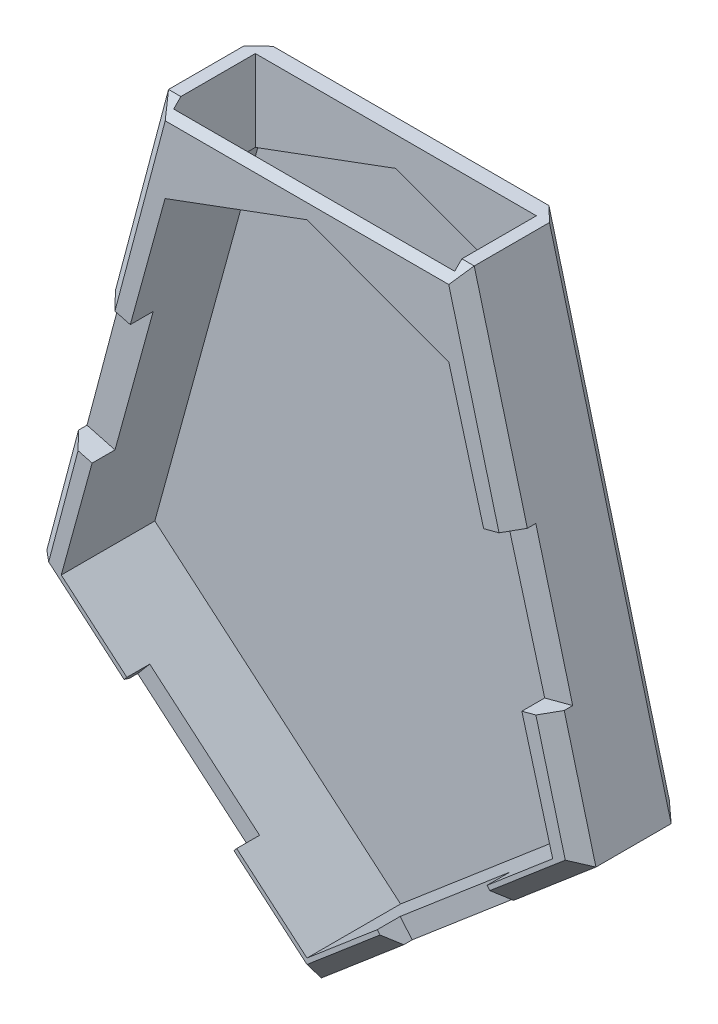
SolidWorks part; units mm, degrees
ref_plane "Front Plane" through (0, 0, 0) normal (0, 0, 1) x (1, 0, 0)
ref_plane "Top Plane" through (0, 0, 0) normal (0, 1, 0) x (1, 0, 0)
ref_plane "Right Plane" through (0, 0, 0) normal (1, 0, 0) x (0, 0, -1)
sketch "Sketch1" plane through (0, 0, 0) normal (0, 0, 1) x (1, 0, 0)
  line L0 (0.1743, 63.7646) -> (-42.2493, 63.7646)
  line L1 (-42.2493, 63.7646) -> (-59.1375, -0.0381)
  line L2 (0.1743, 63.7646) -> (17.0625, -0.0381)
  line L3 (-21.0375, 63.7646) -> (-21.0375, -70.4526) construction
  line L4 (-59.1375, -0.0381) -> (-21.0375, -32.417)
  line L5 (-21.0375, -32.417) -> (17.0625, -0.0381)
  line L6 (-42.2493, 63.7646) -> (17.0625, -0.0381) construction
  line L7 (-59.1375, -0.0381) -> (0.1743, 63.7646) construction
  line L8 (-59.1375, -0.0381) -> (17.0625, -0.0381) construction
  line L9 (-40.73, 52.4141) -> (-21.0375, 59.7084)
  line L10 (-21.0375, 59.7084) -> (-1.3451, 52.4141)
  line L11 (-1.3451, 52.4141) -> (13.0625, -0.0381)
  line L12 (13.0625, -0.0381) -> (-21.0375, -29.0176)
  line L13 (-21.0375, -29.0176) -> (-55.1375, -0.0381)
  line L14 (-55.1375, -0.0381) -> (-40.73, 52.4141)
  dimension "D1" = 76.2
  dimension "D2" = 42.4236
  dimension "D3" = 66
  dimension "D4" = 66
  dimension "D5" = 50
  dimension "D6" = 50
  dimension "D7" = 21
  dimension "D8" = 21
  dimension "D9" = 115
  dimension "D10" = 115
  dimension "D11" = 4
  dimension "D12" = 4
  dimension "D13" = 360
  dimension "D14" = 139.35
  dimension "D15" = 88.726
  dimension "D16" = 125.684
  dimension "D17" = 125.684
  dimension "D18" = 54.395
  dimension "D19" = 44.7507
  dimension "D20" = 99.282
extrude "Boss-Extrude3" add sketch "Sketch1" along normal blind 14.4395 contours L4 L5 L2 L0 L1 L13 L14 L9 L10 L11 L12 region at (7.4322, 31.5493, 0)
extrude "Boss-Extrude4" add sketch "Sketch1<5>" along normal blind 1.4532 contours L14 L13 L12 L11 L10 L9 region at (-21.0375, 16.588, 0)
sketch "Sketch1<5>" plane through (0, 0, 0) normal (0, 0, 1) x (1, 0, 0) same geometry as "Sketch1"
sketch "Sketch3" plane through (0, 63.7646, 0) normal (0, 1, 0) x (1, 0, 0)
  line L1 (-40.5393, -2.1) -> (-1.5393, -2.1)
  line L2 (-40.5393, -2.1) -> (-40.5393, -13.4395)
  line L3 (-40.5393, -13.4395) -> (-1.5393, -13.4395)
  line L4 (-1.5393, -2.1) -> (-1.5393, -13.4395)
  line L5 (-42.2493, -14.4395) -> (-42.2493, 0) construction
  line L7 (0.1743, 0) -> (-42.2493, 0) construction
  line L8 (0.1743, -14.4395) -> (-42.2493, -14.4395) construction
  dimension "D1" = 39
  dimension "D2" = 1.71
  dimension "D3" = 2.1
  dimension "D4" = 1
extrude "Cut-Extrude2" cut sketch "Sketch3" against normal blind 20 contours L2 L1 L4 L3
sketch "Sketch5" plane through (-24.8185, -29.2037, 0) normal (-0.6476, -0.762, 0) x (0.762, -0.6476, 0)
  line L0 (-45.0381, 14.4395) -> (4.9619, 14.4395) construction
  line L1 (-30.0381, 14.4395) -> (-10.0381, 14.4395)
  line L2 (-30.0381, 14.4395) -> (-30.0381, 11.2645)
  line L3 (-30.0381, 11.2645) -> (-10.0381, 11.2645)
  line L4 (-10.0381, 14.4395) -> (-10.0381, 11.2645)
  line L5 (-45.0381, 14.4395) -> (-45.0381, 0) construction
  dimension "D1" = 20
  dimension "D2" = 15
  dimension "D3" = 3.175
sketch "Sketch6" plane through (7.1741, -8.4417, 0) normal (0.6476, -0.762, 0) x (0.762, 0.6476, 0)
  line L0 (-37.0231, 14.4395) -> (12.9769, 14.4395) construction
  line L1 (-22.0231, 14.4395) -> (-2.0231, 14.4395)
  line L2 (-22.0231, 14.4395) -> (-22.0231, 11.2645)
  line L3 (-22.0231, 11.2645) -> (-2.0231, 11.2645)
  line L4 (-2.0231, 14.4395) -> (-2.0231, 11.2645)
  line L5 (12.9769, 14.4395) -> (12.9769, 0) construction
  dimension "D1" = 3.175
  dimension "D2" = 20
  dimension "D3" = 15
extrude "Cut-Extrude3" cut sketch "Sketch6" against normal blind 20
extrude "Cut-Extrude4" cut sketch "Sketch5" against normal blind 20
sketch "Sketch7" plane through (-55.256, 14.6259, 0) normal (-0.9667, 0.2559, 0) x (0, 0, 1)
  line L0 (14.4395, 50.831) -> (14.4395, -15.169) construction
  line L2 (14.4395, -15.169) -> (0, -15.169) construction
  line L3 (14.4395, 22.026) -> (11.2645, 22.026)
  line L4 (14.4395, 22.026) -> (14.4395, 2.026)
  line L5 (14.4395, 2.026) -> (11.2645, 2.026)
  line L6 (11.2645, 22.026) -> (11.2645, 2.026)
  point P2 (12.852, 2.026)
  dimension "D1" = 20
  dimension "D2" = 17.195
  dimension "D3" = 3.175
sketch "Sketch8" plane through (15.9359, 4.2181, 0) normal (0.9667, 0.2559, 0) x (0, 0, -1)
  line L0 (-14.4395, 61.5972) -> (-14.4395, -4.4028) construction
  line L1 (-14.4395, 12.7922) -> (-11.2645, 12.7922)
  line L2 (-14.4395, 12.7922) -> (-14.4395, 32.7922)
  line L3 (-14.4395, 32.7922) -> (-11.2645, 32.7922)
  line L4 (-11.2645, 12.7922) -> (-11.2645, 32.7922)
  line L5 (-14.4395, -4.4028) -> (0, -4.4028) construction
  dimension "D1" = 20
  dimension "D2" = 3.175
  dimension "D3" = 17.195
extrude "Cut-Extrude5" cut sketch "Sketch8" against normal blind 20
extrude "Cut-Extrude6" cut sketch "Sketch7" against normal blind 20
chamfer "Chamfer1" distance 2 angle 45 9 edges at (-56.9376, 8.2732, 14.4395) (-53.4225, -4.8949, 14.4395) (-26.7525, -27.5601, 14.4395) (-15.3225, -27.5601, 14.4395) (11.3475, -4.8949, 14.4395) (14.8625, 8.2732, 14.4395) (3.8596, 49.8416, 14.4395) (-21.0375, 63.7646, 14.4395) (-45.9347, 49.8416, 14.4395)
chamfer "Chamfer2" distance 2 angle 45 4 edges at (-50.6934, 31.8633, 0) (-40.0875, -16.2275, 0) (8.6184, 31.8633, 0) (-1.9875, -16.2275, 0)
